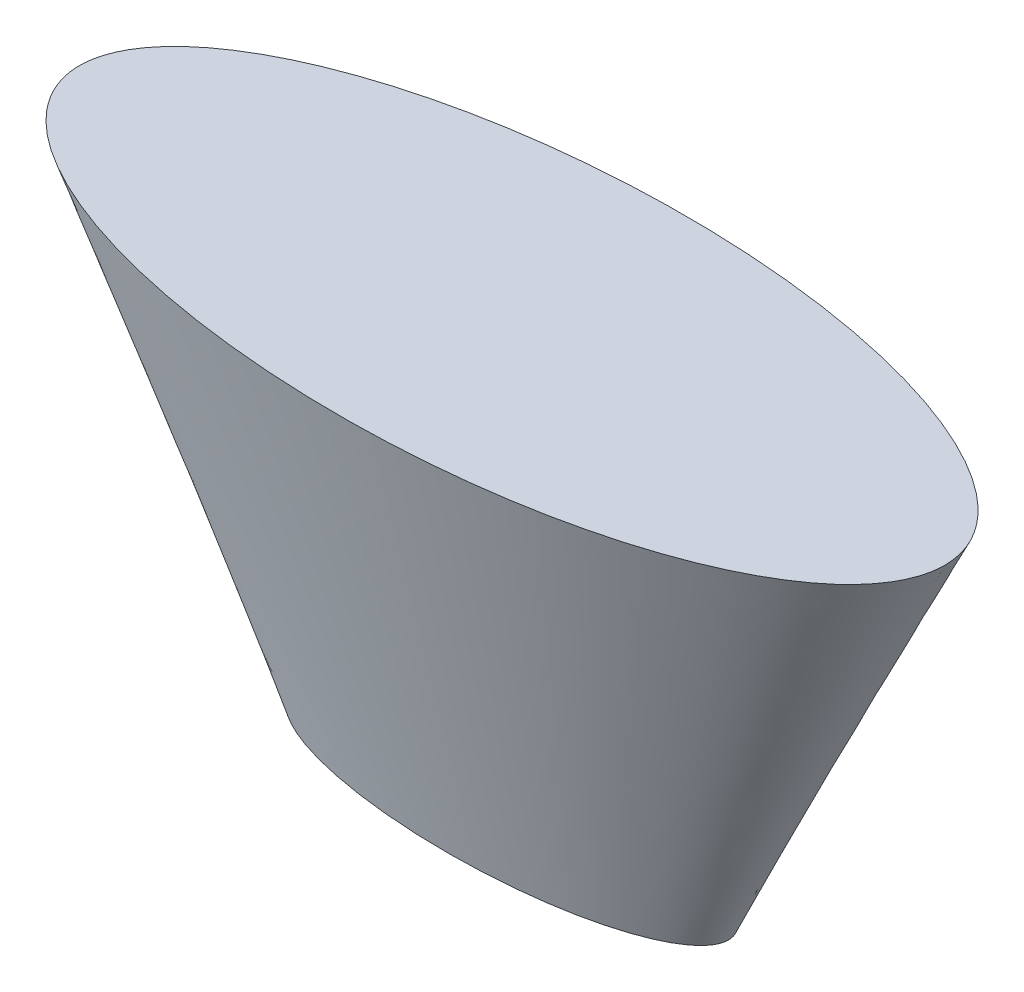
SolidWorks part; units mm, degrees
ref_plane "Plan de face" through (0, 0, 0) normal (0, 0, 1) x (1, 0, 0)
ref_plane "Plan de dessus" through (0, 0, 0) normal (0, 1, 0) x (1, 0, 0)
ref_plane "Plan de droite" through (0, 0, 0) normal (1, 0, 0) x (0, 0, -1)
ref_plane "Plan1" through (0, 10, 0) normal (0, 1, 0) x (1, 0, 0)
ref_plane "Plan2" through (0, -10, 0) normal (0, 1, 0) x (1, 0, 0)
sketch "Esquisse1" plane through (0, 10, 0) normal (0, 1, 0) x (1, 0, 0)
  ellipse E0 centre (0, 0) end of major axis (20, 0) minor radius 8
  point P1 (0, 0)
  dimension "D1" = 40
  dimension "D2" = 16
sketch "Esquisse2" plane through (0, -10, 0) normal (0, 1, 0) x (1, 0, 0)
  ellipse E0 centre (0, 0) end of major axis (10, 0) minor radius 3
  point P1 (0, 0)
  dimension "D1" = 20
  dimension "D2" = 6
loft "Lissage1" add profiles "Esquisse2", "Esquisse1" connector at (-9.6064, -10, -0.8334) connector at (-17.9826, 10, -3.5014)
